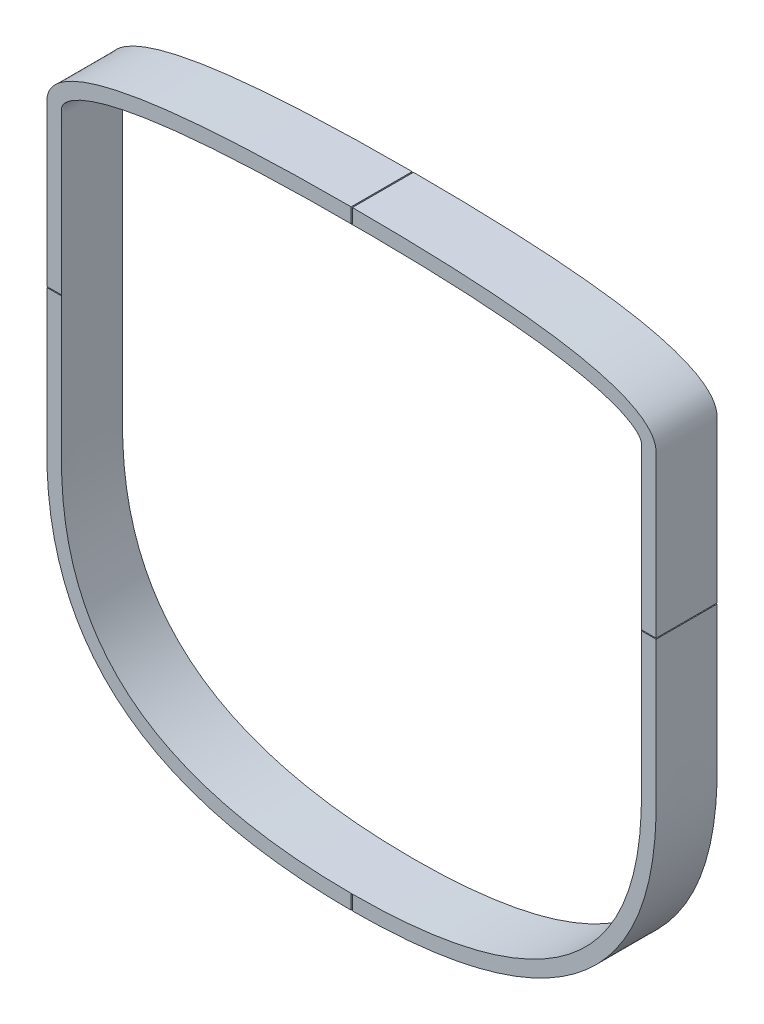
SolidWorks part; units mm, degrees
ref_plane "Front Plane" through (0, 0, 0) normal (0, 0, 1) x (1, 0, 0)
ref_plane "Top Plane" through (0, 0, 0) normal (0, 1, 0) x (1, 0, 0)
ref_plane "Right Plane" through (0, 0, 0) normal (1, 0, 0) x (0, 0, -1)
sketch "Sketch1" plane through (0, 0, 0) normal (0, 0, 1) x (1, 0, 0)
  line L0 (-100.01, 47.0605) -> (-95.145, 47.0605) construction
  line L1 (-95.145, 47.0605) -> (-95.145, 47.3605) construction
  line L2 (-95.145, 47.3605) -> (-100.01, 47.3605) construction
  line L3 (0.3, -80.0112) -> (0.3, -75.1462) construction
  line L4 (0.3, -75.1462) -> (-0.1, -75.1462) construction
  line L5 (-0.1, -75.1462) -> (-0.1, -80.0113) construction
  line L6 (100.01, 47.0605) -> (95.145, 47.0605) construction
  line L7 (95.145, 47.0605) -> (95.145, 47.3605) construction
  line L8 (95.145, 47.3605) -> (100.01, 47.3605) construction
  line L9 (-0.1, 120.0108) -> (-0.1, 115.1456) construction
  line L10 (-0.1, 115.1456) -> (0.3, 115.1456) construction
  line L11 (0.3, 115.1456) -> (0.3, 120) construction
  line L12 (-100.01, 47.0605) -> (-95.145, 47.0605)
  line L13 (-95.145, 47.0605) -> (-95.145, 47.3605)
  line L14 (-95.145, 47.3605) -> (-100.01, 47.3605)
  line L15 (0.3, -80.0112) -> (0.3, -75.1462)
  line L16 (0.3, -75.1462) -> (-0.1, -75.1462)
  line L17 (-0.1, -75.1462) -> (-0.1, -80.0113)
  line L18 (100.01, 47.0605) -> (95.145, 47.0605)
  line L19 (95.145, 47.0605) -> (95.145, 47.3605)
  line L20 (95.145, 47.3605) -> (100.01, 47.3605)
  line L21 (-0.1, 120.0108) -> (-0.1, 115.1456)
  line L22 (-0.1, 115.1456) -> (0.3, 115.1456)
  line L23 (0.3, 115.1456) -> (0.3, 120)
  spline S1 degree 3 poles (99.7997, 99.6773) (99.8036, 99.9509) (99.7918, 100.4046) (99.7567, 100.8662) (99.681, 101.3713) (99.4748, 102.3026) (98.9784, 103.5224) (98.2111, 104.7064) (97.4509, 105.6067) (96.7168, 106.336) (95.7397, 107.1776) (94.5505, 108.0336) (93.1451, 108.8913) (91.7553, 109.627) (90.3759, 110.2763) (88.5549, 111.0479) (86.2863, 111.8842) (83.5821, 112.7336) (80.8863, 113.4732) (77.3062, 114.3386) (72.8372, 115.247) (67.4911, 116.1276) (62.1537, 116.8577) (55.0502, 117.6648) (46.1798, 118.4308) (35.5554, 119.0568) (24.9443, 119.4728) (10.8109, 119.7907) (-3.2959, 119.8408) (-17.4186, 119.6586) (-28.0207, 119.3706) (-38.6348, 118.9) (-49.264, 118.1957) (-58.1353, 117.3502) (-65.2481, 116.4514) (-70.5879, 115.6377) (-75.9423, 114.6434) (-80.4143, 113.6143) (-84.0118, 112.6066) (-86.7154, 111.7373) (-88.9907, 110.8755) (-90.8116, 110.0789) (-92.1968, 109.4029) (-93.5848, 108.6377) (-94.773, 107.876) (-95.7176, 107.1784) (-96.45, 106.576) (-97.1862, 105.883) (-97.9288, 105.0629) (-98.5735, 104.1718) (-99.0633, 103.2704) (-99.3935, 102.4897) (-99.6149, 101.7198) (-99.7273, 101.0847) (-99.7694, 100.7104) (-99.7903, 100.4114) (-99.7992, 100.1667) (-99.8002, 99.9845) (-99.7998, 99.869) (-99.7998, 99.7406) (-99.7998, 99.5238) (-99.8, 99.2514) (-99.8003, 98.8108) (-99.8005, 98.2617) (-99.8006, 97.6024) (-99.8006, 96.7238) (-99.8004, 95.626) (-99.8, 94.3096) (-99.7998, 92.994) (-99.7998, 91.2393) (-99.8, 89.0456) (-99.8002, 86.4124) (-99.8002, 83.7794) (-99.8003, 80.2688) (-99.8002, 75.8805) (-99.8, 70.6147) (-99.7999, 65.349) (-99.7999, 60.0833) (-99.7999, 53.0623) (-99.8, 44.2861) (-99.8001, 33.7545) (-99.8005, 23.2232) (-99.7997, 14.4459) (-99.8011, 7.4266) (-99.7969, 3.0338) (-99.8053, -0.466) (-99.7591, -4.1567) (-99.4387, -10.5423) (-98.2942, -19.73) (-95.5017, -30.6179) (-91.0075, -41.0897) (-84.6521, -50.6636) (-76.6002, -58.8628) (-67.303, -65.4359) (-53.8961, -72.1154) (-36.165, -77.1506) (-18.1876, -79.2977) (-3.835, -79.8498) (10.4785, -79.7642) (28.4686, -78.3932) (49.8925, -73.7834) (67.0953, -66.0502) (79.0866, -56.6481) (86.6805, -48.0163) (92.5016, -38.1179) (96.4764, -27.4833) (98.4332, -18.3609) (99.3377, -11.0291) (99.6551, -6.4456) (99.7809, -2.7913) (99.8043, -0.0384) (99.7991, 2.5844) (99.8005, 6.0917) (99.7999, 10.4829) (99.8001, 17.5023) (99.8, 26.2794) (99.8, 36.8107) (99.8, 47.3423) (99.8, 56.1185) (99.8, 63.1396) (99.8, 68.4053) (99.8, 73.6711) (99.8, 78.9369) (99.8, 83.325) (99.8, 86.8355) (99.8, 89.4684) (99.8, 91.6625) (99.8, 93.4178) (99.8, 94.7342) (99.8, 95.8313) (99.8, 96.7088) (99.8, 97.3675) (99.8, 98.0238) (99.8, 98.5785) (99.8, 99.0062) (99.8001, 99.2955) (99.7997, 99.5144) (99.7997, 99.6773) (99.8036, 99.9509) (99.7918, 100.4046) knots -0.000977 -0.000732 -0.000488 0 0.000244 0.000488 0.000732 0.000977 0.001953 0.00293 0.003906 0.004883 0.005859 0.007812 0.009766 0.011719 0.013672 0.015625 0.019531 0.023438 0.027344 0.03125 0.039062 0.046875 0.054688 0.0625 0.078125 0.09375 0.109375 0.125 0.15625 0.171875 0.1875 0.203125 0.21875 0.234375 0.242188 0.25 0.257812 0.265625 0.269531 0.273438 0.277344 0.279297 0.28125 0.283203 0.285156 0.286133 0.287109 0.288086 0.289062 0.290039 0.290527 0.291016 0.291504 0.291748 0.291992 0.292114 0.292236 0.292358 0.29248 0.292725 0.292969 0.293457 0.293945 0.294922 0.295898 0.296875 0.298828 0.300781 0.302734 0.304688 0.308594 0.3125 0.316406 0.320312 0.328125 0.335938 0.34375 0.351562 0.359375 0.375 0.390625 0.40625 0.421875 0.429688 0.4375 0.441406 0.445312 0.453125 0.46875 0.484375 0.5 0.515625 0.53125 0.546875 0.5625 0.59375 0.625 0.640625 0.65625 0.6875 0.71875 0.75 0.765625 0.78125 0.796875 0.8125 0.828125 0.835938 0.84375 0.847656 0.851562 0.855469 0.859375 0.867188 0.875 0.890625 0.90625 0.921875 0.9375 0.945312 0.953125 0.960938 0.96875 0.976562 0.980469 0.984375 0.988281 0.990234 0.992188 0.994141 0.995117 0.996094 0.99707 0.998047 0.998535 0.999023 0.999268 0.999512 1 1.000244 1.000488 1.000732 only from (99.7993, 100.0793) to (99.7993, 100.0793)
  spline S2 degree 3 poles (99.7997, 99.6773) (99.8036, 99.9509) (99.7918, 100.4046) (99.7567, 100.8662) (99.681, 101.3713) (99.4748, 102.3026) (98.9784, 103.5224) (98.2111, 104.7064) (97.4509, 105.6067) (96.7168, 106.336) (95.7397, 107.1776) (94.5505, 108.0336) (93.1451, 108.8913) (91.7553, 109.627) (90.3759, 110.2763) (88.5549, 111.0479) (86.2863, 111.8842) (83.5821, 112.7336) (80.8863, 113.4732) (77.3062, 114.3386) (72.8372, 115.247) (67.4911, 116.1276) (62.1537, 116.8577) (55.0502, 117.6648) (46.1798, 118.4308) (35.5554, 119.0568) (24.9443, 119.4728) (10.8109, 119.7907) (-3.2959, 119.8408) (-17.4186, 119.6586) (-28.0207, 119.3706) (-38.6348, 118.9) (-49.264, 118.1957) (-58.1353, 117.3502) (-65.2481, 116.4514) (-70.5879, 115.6377) (-75.9423, 114.6434) (-80.4143, 113.6143) (-84.0118, 112.6066) (-86.7154, 111.7373) (-88.9907, 110.8755) (-90.8116, 110.0789) (-92.1968, 109.4029) (-93.5848, 108.6377) (-94.773, 107.876) (-95.7176, 107.1784) (-96.45, 106.576) (-97.1862, 105.883) (-97.9288, 105.0629) (-98.5735, 104.1718) (-99.0633, 103.2704) (-99.3935, 102.4897) (-99.6149, 101.7198) (-99.7273, 101.0847) (-99.7694, 100.7104) (-99.7903, 100.4114) (-99.7992, 100.1667) (-99.8002, 99.9845) (-99.7998, 99.869) (-99.7998, 99.7406) (-99.7998, 99.5238) (-99.8, 99.2514) (-99.8003, 98.8108) (-99.8005, 98.2617) (-99.8006, 97.6024) (-99.8006, 96.7238) (-99.8004, 95.626) (-99.8, 94.3096) (-99.7998, 92.994) (-99.7998, 91.2393) (-99.8, 89.0456) (-99.8002, 86.4124) (-99.8002, 83.7794) (-99.8003, 80.2688) (-99.8002, 75.8805) (-99.8, 70.6147) (-99.7999, 65.349) (-99.7999, 60.0833) (-99.7999, 53.0623) (-99.8, 44.2861) (-99.8001, 33.7545) (-99.8005, 23.2232) (-99.7997, 14.4459) (-99.8011, 7.4266) (-99.7969, 3.0338) (-99.8053, -0.466) (-99.7591, -4.1567) (-99.4387, -10.5423) (-98.2942, -19.73) (-95.5017, -30.6179) (-91.0075, -41.0897) (-84.6521, -50.6636) (-76.6002, -58.8628) (-67.303, -65.4359) (-53.8961, -72.1154) (-36.165, -77.1506) (-18.1876, -79.2977) (-3.835, -79.8498) (10.4785, -79.7642) (28.4686, -78.3932) (49.8925, -73.7834) (67.0953, -66.0502) (79.0866, -56.6481) (86.6805, -48.0163) (92.5016, -38.1179) (96.4764, -27.4833) (98.4332, -18.3609) (99.3377, -11.0291) (99.6551, -6.4456) (99.7809, -2.7913) (99.8043, -0.0384) (99.7991, 2.5844) (99.8005, 6.0917) (99.7999, 10.4829) (99.8001, 17.5023) (99.8, 26.2794) (99.8, 36.8107) (99.8, 47.3423) (99.8, 56.1185) (99.8, 63.1396) (99.8, 68.4053) (99.8, 73.6711) (99.8, 78.9369) (99.8, 83.325) (99.8, 86.8355) (99.8, 89.4684) (99.8, 91.6625) (99.8, 93.4178) (99.8, 94.7342) (99.8, 95.8313) (99.8, 96.7088) (99.8, 97.3675) (99.8, 98.0238) (99.8, 98.5785) (99.8, 99.0062) (99.8001, 99.2955) (99.7997, 99.5144) (99.7997, 99.6773) (99.8036, 99.9509) (99.7918, 100.4046) knots -0.000977 -0.000732 -0.000488 0 0.000244 0.000488 0.000732 0.000977 0.001953 0.00293 0.003906 0.004883 0.005859 0.007812 0.009766 0.011719 0.013672 0.015625 0.019531 0.023438 0.027344 0.03125 0.039062 0.046875 0.054688 0.0625 0.078125 0.09375 0.109375 0.125 0.15625 0.171875 0.1875 0.203125 0.21875 0.234375 0.242188 0.25 0.257812 0.265625 0.269531 0.273438 0.277344 0.279297 0.28125 0.283203 0.285156 0.286133 0.287109 0.288086 0.289062 0.290039 0.290527 0.291016 0.291504 0.291748 0.291992 0.292114 0.292236 0.292358 0.29248 0.292725 0.292969 0.293457 0.293945 0.294922 0.295898 0.296875 0.298828 0.300781 0.302734 0.304688 0.308594 0.3125 0.316406 0.320312 0.328125 0.335938 0.34375 0.351562 0.359375 0.375 0.390625 0.40625 0.421875 0.429688 0.4375 0.441406 0.445312 0.453125 0.46875 0.484375 0.5 0.515625 0.53125 0.546875 0.5625 0.59375 0.625 0.640625 0.65625 0.6875 0.71875 0.75 0.765625 0.78125 0.796875 0.8125 0.828125 0.835938 0.84375 0.847656 0.851562 0.855469 0.859375 0.867188 0.875 0.890625 0.90625 0.921875 0.9375 0.945312 0.953125 0.960938 0.96875 0.976562 0.980469 0.984375 0.988281 0.990234 0.992188 0.994141 0.995117 0.996094 0.99707 0.998047 0.998535 0.999023 0.999268 0.999512 1 1.000244 1.000488 1.000732 only from (99.7993, 100.0793) to (99.7993, 100.0793)
  spline S3 degree 3 poles (94.9991, 99.6498) (95.0033, 99.9945) (94.9886, 100.3305) (94.9285, 100.6507) (94.8294, 100.9604) (94.5623, 101.5544) (93.9794, 102.3192) (93.0263, 103.2069) (91.6762, 104.1962) (89.7643, 105.2891) (86.7225, 106.6551) (82.5543, 108.083) (76.1132, 109.7535) (67.4455, 111.3546) (54.2601, 113.0179) (36.6733, 114.3033) (21.0967, 114.796) (10.1079, 114.9512) (4.9035, 114.9925) (-0.3225, 115.0048) (-7.3652, 114.9836) (-16.0311, 114.8829) (-26.9636, 114.6065) (-37.956, 114.1366) (-48.8577, 113.4115) (-58.667, 112.4743) (-66.6295, 111.4261) (-72.9317, 110.3437) (-78.1678, 109.2363) (-83.1304, 107.9121) (-87.3123, 106.426) (-90.3426, 104.9929) (-92.2115, 103.8445) (-93.3583, 102.913) (-93.9767, 102.2848) (-94.5313, 101.602) (-94.8966, 100.9077) (-94.9869, 100.3092) (-95.0003, 100.0907) (-94.9996, 99.7607) (-95.0013, 97.7241) (-94.9995, 93.9804) (-95.0006, 84.2276) (-94.9997, 68.373) (-95, 40.1872) (-95.0005, 17.4761) (-94.9999, 2.1967) (-95.0002, 0.4352) (-94.9982, -2.3323) (-94.8101, -8.1993) (-93.8713, -17.1447) (-91.4322, -27.5753) (-87.8502, -36.4563) (-83.6838, -43.555) (-79.3185, -49.2124) (-73.5088, -55.0355) (-65.8142, -60.7188) (-56.8099, -65.3701) (-47.6395, -68.7951) (-37.8771, -71.4534) (-26.8877, -73.4301) (-15.4181, -74.5813) (-6.1485, -74.9679) (0.8919, -75.0173) (7.9604, -74.9151) (16.7848, -74.4683) (27.3133, -73.3359) (37.741, -71.4746) (51.3819, -67.8285) (64.4819, -61.969) (74.2954, -54.3104) (79.226, -49.2152) (83.6031, -43.7463) (88.1341, -36.0845) (91.8283, -26.2136) (94.0819, -15.7449) (94.8156, -7.8256) (94.9715, -2.8766) (94.9968, -1.1263) (95.0018, 0.6243) (94.9994, 2.8316) (95.0003, 6.3331) (94.9999, 10.7101) (95, 14.3284) (95, 16.3126) (95, 16.6627) (95, 17.0129) (95, 17.3631) (95, 17.7132) (95, 18.0634) (95, 18.4135) (95, 18.7637) (95, 19.1138) (95, 19.464) (95, 19.8142) (95, 20.1643) (95, 20.5145) (95, 20.8646) (95, 21.2148) (95, 21.5649) (95, 21.9151) (95, 22.2652) (95, 22.6154) (95, 22.9656) (95, 23.3157) (95, 23.6659) (95, 24.016) (95, 24.3662) (95, 24.7163) (95, 25.0665) (95, 25.4167) (95, 25.7668) (95, 26.117) (95, 26.4671) (95, 26.8173) (95, 27.1674) (95, 27.5176) (95, 27.8678) (95, 28.2179) (95, 28.5681) (95, 28.9182) (95, 29.2684) (95, 29.6185) (95, 29.9687) (95, 30.3188) (95, 30.669) (95, 31.0192) (95, 31.3693) (95, 31.7195) (95, 32.0696) (95, 32.4198) (95, 32.7699) (95, 33.1201) (95, 33.4703) (95, 33.8204) (95, 34.1706) (95, 34.5207) (95, 34.8709) (95, 35.221) (95, 35.5712) (95, 35.9213) (95, 36.2715) (95, 36.6217) (95, 36.9718) (95, 37.322) (95, 37.6721) (95, 38.0223) (95, 38.3724) (95, 38.7226) (95, 39.0728) (95, 39.4229) (95, 39.7731) (95, 40.1232) (95, 40.4734) (95, 40.8235) (95, 41.1737) (95, 41.5239) (95, 41.874) (95, 42.2242) (95, 42.5743) (95, 42.9245) (95, 43.2746) (95, 43.6248) (95, 43.9749) (95, 44.3251) (95, 44.6753) (95, 45.0254) (95, 45.3756) (95, 45.7257) (95, 46.0759) (95, 46.426) (95, 46.7762) (95, 47.1264) (95, 47.4765) (95, 47.8267) (95, 48.1768) (95, 48.527) (95, 48.8771) (95, 49.2273) (95, 49.5774) (95, 49.9276) (95, 50.2778) (95, 50.6279) (95, 50.9781) (95, 51.3282) (95, 51.6784) (95, 52.0285) (95, 52.3787) (95, 52.7289) (95, 53.079) (95, 53.4292) (95, 53.7793) (95, 54.1295) (95, 54.4796) (95, 54.8298) (95, 55.18) (95, 55.5301) (95, 55.8803) (95, 56.2304) (95, 56.5806) (95, 56.9307) (95, 57.2809) (95, 57.631) (95, 57.9812) (95, 58.3314) (95, 58.6815) (95, 59.0317) (95, 59.3818) (95, 59.732) (95, 60.0821) (95, 60.4323) (95, 60.7825) (95, 61.1326) (95, 61.4828) (95, 61.8329) (95, 62.1831) (95, 62.5332) (95, 62.8834) (95, 63.2336) (95, 63.5837) (95, 63.9339) (95, 64.284) (95, 64.6342) (95, 64.9843) (95, 65.3345) (95, 65.6846) (95, 66.0348) (95, 66.385) (95, 66.7351) (95, 67.0853) (95, 67.4354) (95, 67.7856) (95, 68.1357) (95, 68.4859) (95, 68.8361) (95, 69.1862) (95, 69.5364) (95, 69.8865) (95, 70.2367) (95, 70.5868) (95, 70.937) (95, 71.2871) (95, 71.6373) (95, 71.9875) (95, 72.3376) (95, 72.6878) (95, 73.0379) (95, 73.3881) (95, 73.7382) (95, 74.0884) (95, 74.4386) (95, 74.7887) (95, 75.1389) (95, 75.489) (95, 75.8392) (95, 76.1893) (95, 76.5395) (95, 76.8897) (95, 77.2398) (95, 77.59) (95, 77.9401) (95, 78.2903) (95, 78.6404) (95, 78.9906) (95, 79.3407) (95, 79.6909) (95, 80.0411) (95, 80.3912) (95, 80.7414) (95, 81.0915) (95, 81.4417) (95, 81.7918) (95, 82.142) (95, 82.4922) (95, 82.8423) (95, 83.1925) (95, 83.5426) (95, 83.8928) (95, 84.2429) (95, 84.5931) (95, 84.9432) (95, 85.2934) (95, 85.6436) (95, 85.9937) (95, 86.3439) (95, 86.694) (95, 87.0442) (95, 87.3943) (95, 87.7445) (95, 88.0947) (95, 88.4448) (95, 88.795) (95, 89.1451) (95, 89.4953) (95, 89.8454) (95, 90.1956) (95, 90.5458) (95, 90.8959) (95, 91.2461) (95, 91.5962) (95, 91.9464) (95, 92.2965) (95, 92.6467) (95, 92.9968) (95, 93.347) (95, 93.6972) (95, 94.0473) (95, 94.3975) (95, 94.7476) (95, 95.0978) (95, 95.4479) (95, 95.7981) (95, 96.1483) (95, 96.4984) (95, 96.8486) (95, 97.1987) (95, 97.5489) (95, 97.899) (95, 98.2492) (95, 98.5994) (94.9999, 98.9495) (95.0002, 99.2997) (94.9991, 99.6498) (95.0033, 99.9945) (94.9886, 100.3305) knots -0.001559 -0.001039 -0.00052 0 0.000495 0.000974 0.001446 0.001939 0.003867 0.005664 0.00773 0.011301 0.015445 0.022555 0.030881 0.045044 0.061752 0.090013 0.123492 0.131103 0.138928 0.146657 0.154364 0.170275 0.185229 0.203037 0.219242 0.233854 0.246889 0.254977 0.26231 0.270704 0.277822 0.282028 0.285605 0.287554 0.288589 0.28952 0.291476 0.291962 0.292206 0.29245 0.293431 0.301271 0.309112 0.33684 0.371839 0.434565 0.437925 0.439846 0.442406 0.450243 0.465965 0.482358 0.497762 0.508388 0.518904 0.52948 0.544908 0.56127 0.574423 0.588416 0.606248 0.624055 0.639683 0.647525 0.655389 0.671146 0.686832 0.702495 0.718232 0.749659 0.765474 0.773344 0.781173 0.796611 0.812727 0.82787 0.84415 0.848045 0.849909 0.851941 0.855837 0.859734 0.867526 0.875319 0.875838 0.876358 0.876877 0.877397 0.877916 0.878436 0.878955 0.879475 0.879994 0.880514 0.881033 0.881553 0.882072 0.882592 0.883111 0.883631 0.88415 0.88467 0.885189 0.885709 0.886228 0.886748 0.887267 0.887787 0.888306 0.888826 0.889345 0.889865 0.890384 0.890904 0.891423 0.891943 0.892462 0.892982 0.893501 0.894021 0.89454 0.89506 0.895579 0.896099 0.896618 0.897138 0.897657 0.898177 0.898696 0.899216 0.899735 0.900255 0.900774 0.901294 0.901813 0.902333 0.902852 0.903372 0.903891 0.904411 0.90493 0.90545 0.90597 0.906489 0.907009 0.907528 0.908048 0.908567 0.909087 0.909606 0.910126 0.910645 0.911165 0.911684 0.912204 0.912723 0.913243 0.913762 0.914282 0.914801 0.915321 0.91584 0.91636 0.916879 0.917399 0.917918 0.918438 0.918957 0.919477 0.919996 0.920516 0.921035 0.921555 0.922074 0.922594 0.923113 0.923633 0.924152 0.924672 0.925191 0.925711 0.92623 0.92675 0.927269 0.927789 0.928308 0.928828 0.929347 0.929867 0.930386 0.930906 0.931425 0.931945 0.932464 0.932984 0.933503 0.934023 0.934542 0.935062 0.935581 0.936101 0.93662 0.93714 0.937659 0.938179 0.938698 0.939218 0.939737 0.940257 0.940776 0.941296 0.941815 0.942335 0.942854 0.943374 0.943893 0.944413 0.944932 0.945452 0.945971 0.946491 0.94701 0.94753 0.948049 0.948569 0.949088 0.949608 0.950127 0.950647 0.951166 0.951686 0.952205 0.952725 0.953245 0.953764 0.954284 0.954803 0.955323 0.955842 0.956362 0.956881 0.957401 0.95792 0.95844 0.958959 0.959479 0.959998 0.960518 0.961037 0.961557 0.962076 0.962596 0.963115 0.963635 0.964154 0.964674 0.965193 0.965713 0.966232 0.966752 0.967271 0.967791 0.96831 0.96883 0.969349 0.969869 0.970388 0.970908 0.971427 0.971947 0.972466 0.972986 0.973505 0.974025 0.974544 0.975064 0.975583 0.976103 0.976622 0.977142 0.977661 0.978181 0.9787 0.97922 0.979739 0.980259 0.980778 0.981298 0.981817 0.982337 0.982856 0.983376 0.983895 0.984415 0.984934 0.985454 0.985973 0.986493 0.987012 0.987532 0.988051 0.988571 0.98909 0.98961 0.990129 0.990649 0.991168 0.991688 0.992207 0.992727 0.993246 0.993766 0.994285 0.994805 0.995324 0.995844 0.996363 0.996883 0.997402 0.997922 0.998441 0.998961 0.99948 1 1.000495 1.000974 1.001446 only from (95, 100) to (95, 100)
  spline S4 degree 3 poles (94.9991, 99.6498) (95.0033, 99.9945) (94.9886, 100.3305) (94.9285, 100.6507) (94.8294, 100.9604) (94.5623, 101.5544) (93.9794, 102.3192) (93.0263, 103.2069) (91.6762, 104.1962) (89.7643, 105.2891) (86.7225, 106.6551) (82.5543, 108.083) (76.1132, 109.7535) (67.4455, 111.3546) (54.2601, 113.0179) (36.6733, 114.3033) (21.0967, 114.796) (10.1079, 114.9512) (4.9035, 114.9925) (-0.3225, 115.0048) (-7.3652, 114.9836) (-16.0311, 114.8829) (-26.9636, 114.6065) (-37.956, 114.1366) (-48.8577, 113.4115) (-58.667, 112.4743) (-66.6295, 111.4261) (-72.9317, 110.3437) (-78.1678, 109.2363) (-83.1304, 107.9121) (-87.3123, 106.426) (-90.3426, 104.9929) (-92.2115, 103.8445) (-93.3583, 102.913) (-93.9767, 102.2848) (-94.5313, 101.602) (-94.8966, 100.9077) (-94.9869, 100.3092) (-95.0003, 100.0907) (-94.9996, 99.7607) (-95.0013, 97.7241) (-94.9995, 93.9804) (-95.0006, 84.2276) (-94.9997, 68.373) (-95, 40.1872) (-95.0005, 17.4761) (-94.9999, 2.1967) (-95.0002, 0.4352) (-94.9982, -2.3323) (-94.8101, -8.1993) (-93.8713, -17.1447) (-91.4322, -27.5753) (-87.8502, -36.4563) (-83.6838, -43.555) (-79.3185, -49.2124) (-73.5088, -55.0355) (-65.8142, -60.7188) (-56.8099, -65.3701) (-47.6395, -68.7951) (-37.8771, -71.4534) (-26.8877, -73.4301) (-15.4181, -74.5813) (-6.1485, -74.9679) (0.8919, -75.0173) (7.9604, -74.9151) (16.7848, -74.4683) (27.3133, -73.3359) (37.741, -71.4746) (51.3819, -67.8285) (64.4819, -61.969) (74.2954, -54.3104) (79.226, -49.2152) (83.6031, -43.7463) (88.1341, -36.0845) (91.8283, -26.2136) (94.0819, -15.7449) (94.8156, -7.8256) (94.9715, -2.8766) (94.9968, -1.1263) (95.0018, 0.6243) (94.9994, 2.8316) (95.0003, 6.3331) (94.9999, 10.7101) (95, 14.3284) (95, 16.3126) (95, 16.6627) (95, 17.0129) (95, 17.3631) (95, 17.7132) (95, 18.0634) (95, 18.4135) (95, 18.7637) (95, 19.1138) (95, 19.464) (95, 19.8142) (95, 20.1643) (95, 20.5145) (95, 20.8646) (95, 21.2148) (95, 21.5649) (95, 21.9151) (95, 22.2652) (95, 22.6154) (95, 22.9656) (95, 23.3157) (95, 23.6659) (95, 24.016) (95, 24.3662) (95, 24.7163) (95, 25.0665) (95, 25.4167) (95, 25.7668) (95, 26.117) (95, 26.4671) (95, 26.8173) (95, 27.1674) (95, 27.5176) (95, 27.8678) (95, 28.2179) (95, 28.5681) (95, 28.9182) (95, 29.2684) (95, 29.6185) (95, 29.9687) (95, 30.3188) (95, 30.669) (95, 31.0192) (95, 31.3693) (95, 31.7195) (95, 32.0696) (95, 32.4198) (95, 32.7699) (95, 33.1201) (95, 33.4703) (95, 33.8204) (95, 34.1706) (95, 34.5207) (95, 34.8709) (95, 35.221) (95, 35.5712) (95, 35.9213) (95, 36.2715) (95, 36.6217) (95, 36.9718) (95, 37.322) (95, 37.6721) (95, 38.0223) (95, 38.3724) (95, 38.7226) (95, 39.0728) (95, 39.4229) (95, 39.7731) (95, 40.1232) (95, 40.4734) (95, 40.8235) (95, 41.1737) (95, 41.5239) (95, 41.874) (95, 42.2242) (95, 42.5743) (95, 42.9245) (95, 43.2746) (95, 43.6248) (95, 43.9749) (95, 44.3251) (95, 44.6753) (95, 45.0254) (95, 45.3756) (95, 45.7257) (95, 46.0759) (95, 46.426) (95, 46.7762) (95, 47.1264) (95, 47.4765) (95, 47.8267) (95, 48.1768) (95, 48.527) (95, 48.8771) (95, 49.2273) (95, 49.5774) (95, 49.9276) (95, 50.2778) (95, 50.6279) (95, 50.9781) (95, 51.3282) (95, 51.6784) (95, 52.0285) (95, 52.3787) (95, 52.7289) (95, 53.079) (95, 53.4292) (95, 53.7793) (95, 54.1295) (95, 54.4796) (95, 54.8298) (95, 55.18) (95, 55.5301) (95, 55.8803) (95, 56.2304) (95, 56.5806) (95, 56.9307) (95, 57.2809) (95, 57.631) (95, 57.9812) (95, 58.3314) (95, 58.6815) (95, 59.0317) (95, 59.3818) (95, 59.732) (95, 60.0821) (95, 60.4323) (95, 60.7825) (95, 61.1326) (95, 61.4828) (95, 61.8329) (95, 62.1831) (95, 62.5332) (95, 62.8834) (95, 63.2336) (95, 63.5837) (95, 63.9339) (95, 64.284) (95, 64.6342) (95, 64.9843) (95, 65.3345) (95, 65.6846) (95, 66.0348) (95, 66.385) (95, 66.7351) (95, 67.0853) (95, 67.4354) (95, 67.7856) (95, 68.1357) (95, 68.4859) (95, 68.8361) (95, 69.1862) (95, 69.5364) (95, 69.8865) (95, 70.2367) (95, 70.5868) (95, 70.937) (95, 71.2871) (95, 71.6373) (95, 71.9875) (95, 72.3376) (95, 72.6878) (95, 73.0379) (95, 73.3881) (95, 73.7382) (95, 74.0884) (95, 74.4386) (95, 74.7887) (95, 75.1389) (95, 75.489) (95, 75.8392) (95, 76.1893) (95, 76.5395) (95, 76.8897) (95, 77.2398) (95, 77.59) (95, 77.9401) (95, 78.2903) (95, 78.6404) (95, 78.9906) (95, 79.3407) (95, 79.6909) (95, 80.0411) (95, 80.3912) (95, 80.7414) (95, 81.0915) (95, 81.4417) (95, 81.7918) (95, 82.142) (95, 82.4922) (95, 82.8423) (95, 83.1925) (95, 83.5426) (95, 83.8928) (95, 84.2429) (95, 84.5931) (95, 84.9432) (95, 85.2934) (95, 85.6436) (95, 85.9937) (95, 86.3439) (95, 86.694) (95, 87.0442) (95, 87.3943) (95, 87.7445) (95, 88.0947) (95, 88.4448) (95, 88.795) (95, 89.1451) (95, 89.4953) (95, 89.8454) (95, 90.1956) (95, 90.5458) (95, 90.8959) (95, 91.2461) (95, 91.5962) (95, 91.9464) (95, 92.2965) (95, 92.6467) (95, 92.9968) (95, 93.347) (95, 93.6972) (95, 94.0473) (95, 94.3975) (95, 94.7476) (95, 95.0978) (95, 95.4479) (95, 95.7981) (95, 96.1483) (95, 96.4984) (95, 96.8486) (95, 97.1987) (95, 97.5489) (95, 97.899) (95, 98.2492) (95, 98.5994) (94.9999, 98.9495) (95.0002, 99.2997) (94.9991, 99.6498) (95.0033, 99.9945) (94.9886, 100.3305) knots -0.001559 -0.001039 -0.00052 0 0.000495 0.000974 0.001446 0.001939 0.003867 0.005664 0.00773 0.011301 0.015445 0.022555 0.030881 0.045044 0.061752 0.090013 0.123492 0.131103 0.138928 0.146657 0.154364 0.170275 0.185229 0.203037 0.219242 0.233854 0.246889 0.254977 0.26231 0.270704 0.277822 0.282028 0.285605 0.287554 0.288589 0.28952 0.291476 0.291962 0.292206 0.29245 0.293431 0.301271 0.309112 0.33684 0.371839 0.434565 0.437925 0.439846 0.442406 0.450243 0.465965 0.482358 0.497762 0.508388 0.518904 0.52948 0.544908 0.56127 0.574423 0.588416 0.606248 0.624055 0.639683 0.647525 0.655389 0.671146 0.686832 0.702495 0.718232 0.749659 0.765474 0.773344 0.781173 0.796611 0.812727 0.82787 0.84415 0.848045 0.849909 0.851941 0.855837 0.859734 0.867526 0.875319 0.875838 0.876358 0.876877 0.877397 0.877916 0.878436 0.878955 0.879475 0.879994 0.880514 0.881033 0.881553 0.882072 0.882592 0.883111 0.883631 0.88415 0.88467 0.885189 0.885709 0.886228 0.886748 0.887267 0.887787 0.888306 0.888826 0.889345 0.889865 0.890384 0.890904 0.891423 0.891943 0.892462 0.892982 0.893501 0.894021 0.89454 0.89506 0.895579 0.896099 0.896618 0.897138 0.897657 0.898177 0.898696 0.899216 0.899735 0.900255 0.900774 0.901294 0.901813 0.902333 0.902852 0.903372 0.903891 0.904411 0.90493 0.90545 0.90597 0.906489 0.907009 0.907528 0.908048 0.908567 0.909087 0.909606 0.910126 0.910645 0.911165 0.911684 0.912204 0.912723 0.913243 0.913762 0.914282 0.914801 0.915321 0.91584 0.91636 0.916879 0.917399 0.917918 0.918438 0.918957 0.919477 0.919996 0.920516 0.921035 0.921555 0.922074 0.922594 0.923113 0.923633 0.924152 0.924672 0.925191 0.925711 0.92623 0.92675 0.927269 0.927789 0.928308 0.928828 0.929347 0.929867 0.930386 0.930906 0.931425 0.931945 0.932464 0.932984 0.933503 0.934023 0.934542 0.935062 0.935581 0.936101 0.93662 0.93714 0.937659 0.938179 0.938698 0.939218 0.939737 0.940257 0.940776 0.941296 0.941815 0.942335 0.942854 0.943374 0.943893 0.944413 0.944932 0.945452 0.945971 0.946491 0.94701 0.94753 0.948049 0.948569 0.949088 0.949608 0.950127 0.950647 0.951166 0.951686 0.952205 0.952725 0.953245 0.953764 0.954284 0.954803 0.955323 0.955842 0.956362 0.956881 0.957401 0.95792 0.95844 0.958959 0.959479 0.959998 0.960518 0.961037 0.961557 0.962076 0.962596 0.963115 0.963635 0.964154 0.964674 0.965193 0.965713 0.966232 0.966752 0.967271 0.967791 0.96831 0.96883 0.969349 0.969869 0.970388 0.970908 0.971427 0.971947 0.972466 0.972986 0.973505 0.974025 0.974544 0.975064 0.975583 0.976103 0.976622 0.977142 0.977661 0.978181 0.9787 0.97922 0.979739 0.980259 0.980778 0.981298 0.981817 0.982337 0.982856 0.983376 0.983895 0.984415 0.984934 0.985454 0.985973 0.986493 0.987012 0.987532 0.988051 0.988571 0.98909 0.98961 0.990129 0.990649 0.991168 0.991688 0.992207 0.992727 0.993246 0.993766 0.994285 0.994805 0.995324 0.995844 0.996363 0.996883 0.997402 0.997922 0.998441 0.998961 0.99948 1 1.000495 1.000974 1.001446 only from (95, 100) to (95, 100)
  dimension "D1" = 0
  dimension "D2" = 0
extrude "Boss-Extrude1" add sketch "Sketch1" along normal mid plane 20 contours L21 S2 L14 L13 L12 L17 L16 L15 L18 L19 L20 L23 L22 S4 region at (-97.4725, 49.8833, 0)
